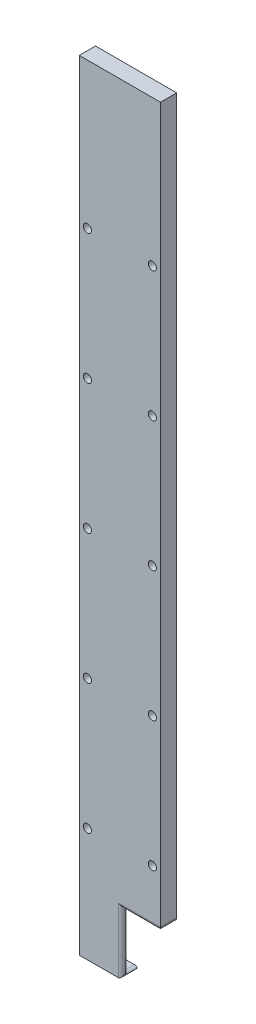
SolidWorks part; units mm, degrees
ref_plane "Front Plane" through (0, 0, 0) normal (0, 0, 1) x (1, 0, 0)
ref_plane "Top Plane" through (0, 0, 0) normal (0, 1, 0) x (1, 0, 0)
ref_plane "Right Plane" through (0, 0, 0) normal (1, 0, 0) x (0, 0, -1)
sketch "Sketch1" plane through (0, 0, 0) normal (0, 0, 1) x (1, 0, 0)
  line L0 (98.3794, 205.2) -> (2.4412, 205.2)
  line L1 (2.4412, 205.2) -> (0.8, 203.5588)
  line L2 (0.8, 203.5588) -> (0.8, 153.025)
  line L3 (0.8, 153.025) -> (2.4412, 151.3838)
  line L8 (86, 134.5838) -> (20, 134.5838) construction
  line L9 (86, 98.5838) -> (86, 134.5838) construction
  line L10 (20, 98.5838) -> (86, 98.5838) construction
  line L11 (20, 134.5838) -> (20, 98.5838) construction
  line L16 (81.145, 81.5838) -> (24.855, 81.5838) construction
  line L17 (84.315, 59.3538) -> (84.315, 78.4138) construction
  line L28 (2.524, 205) -> (1, 203.476) construction
  line L29 (1, 203.476) -> (1, 153.1078) construction
  line L30 (1, 153.1078) -> (2.524, 151.5838) construction
  line L31 (2.524, 151.5838) -> (99.044, 151.5838) construction
  line L32 (99.044, 151.5838) -> (102.6, 155.1398) construction
  line L33 (102.6, 155.1398) -> (102.6, 189.76) construction
  line L34 (102.6, 189.76) -> (100.06, 192.3) construction
  line L35 (100.06, 192.3) -> (100.06, 203.2366) construction
  line L36 (100.06, 203.2366) -> (98.2966, 205) construction
  line L37 (98.2966, 205) -> (2.524, 205) construction
  line L38 (24.855, 56.1838) -> (81.145, 56.1838) construction
  line L39 (21.685, 78.4138) -> (21.685, 59.3538) construction
  line L44 (37.25, 17.6838) -> (68.75, 17.6838) construction
  line L45 (68.75, 17.6838) -> (68.75, 39.1838) construction
  line L46 (68.75, 39.1838) -> (37.25, 39.1838) construction
  line L47 (37.25, 39.1838) -> (37.25, 17.6838) construction
  line L48 (2.4412, 151.3838) -> (99.1268, 151.3838)
  line L49 (99.1268, 151.3838) -> (102.8, 155.057)
  line L50 (102.8, 155.057) -> (102.8, 189.8428) construction
  line L51 (102.8, 189.8428) -> (100.26, 192.3828)
  line L52 (100.26, 192.3828) -> (100.26, 203.3194)
  line L53 (100.26, 203.3194) -> (98.3794, 205.2)
  line L54 (86.2, 134.7838) -> (19.8, 134.7838)
  line L55 (19.8, 134.7838) -> (19.8, 98.3838)
  line L56 (19.8, 98.3838) -> (86.2, 98.3838)
  line L57 (86.2, 98.3838) -> (86.2, 134.7838) construction
  line L58 (81.145, 81.7838) -> (24.855, 81.7838)
  line L59 (21.485, 78.4138) -> (21.485, 59.3538)
  line L60 (24.855, 55.9838) -> (81.145, 55.9838)
  line L61 (84.515, 59.3538) -> (84.515, 78.4138) construction
  line L62 (68.95, 17.4838) -> (68.95, 39.3838) construction
  line L63 (68.95, 39.3838) -> (37.05, 39.3838)
  line L64 (37.05, 39.3838) -> (37.05, 17.4838)
  line L65 (37.05, 17.4838) -> (68.95, 17.4838)
  line L66 (110.8, 177.4499) -> (102.8, 177.4499)
  line L67 (102.8, 177.4499) -> (102.8, 189.8428)
  line L68 (112.8, 175.4499) -> (112.8, 169.4499)
  line L69 (110.8, 167.4499) -> (102.8, 167.4499)
  line L70 (102.8, 155.057) -> (102.8, 167.4499)
  line L71 (86.2, 98.3838) -> (86.2, 111.5838)
  line L72 (86.2, 121.5838) -> (94.2, 121.5838)
  line L73 (96.2, 119.5838) -> (96.2, 113.5838)
  line L74 (94.2, 111.5838) -> (86.2, 111.5838)
  line L75 (86.2, 134.7838) -> (86.2, 121.5838)
  line L77 (84.515, 73.8838) -> (92.515, 73.8838)
  line L78 (94.515, 71.8838) -> (94.515, 65.8838)
  line L79 (92.515, 63.8838) -> (84.515, 63.8838)
  line L80 (84.515, 63.8838) -> (84.515, 59.3538)
  line L81 (68.95, 39.3838) -> (68.95, 34.3838)
  line L82 (68.95, 34.3838) -> (76.95, 34.3838)
  line L83 (78.95, 32.3838) -> (78.95, 24.4838)
  line L84 (76.95, 22.4838) -> (68.95, 22.4838)
  line L85 (68.95, 22.4838) -> (68.95, 17.4838)
  line L89 (102.6, 172.4499) -> (112.8, 172.4499) construction
  line L90 (84.515, 73.8838) -> (84.515, 78.4138)
  line L91 (140, 205.2) -> (150, 205.2) construction
  line L92 (125, 205.2) -> (140, 205.2)
  line L93 (125, 205.2) -> (125, 0)
  line L94 (125, 0) -> (140, 0)
  line L95 (140, 205.2) -> (140, 0)
  line L97 (132.5, 205.2) -> (132.5, 0) construction
  line L99 (142.5, 205.2) -> (142.5, 0) construction
  arc A0 (24.855, 81.7838) -> (21.485, 78.4138) centre (24.855, 78.4138) ccw
  circle A2 centre (22.5, 132.0838) radius 1.6 construction
  circle A4 centre (15.1224, 202.46) radius 1.5621 construction
  circle A6 centre (15.1224, 154.1238) radius 1.5621 construction
  circle A8 centre (97.7486, 154.1238) radius 1.5621 construction
  circle A10 centre (22.5, 101.0838) radius 1.6 construction
  circle A12 centre (83.5, 101.0838) radius 1.6 construction
  circle A14 centre (83.5, 132.0838) radius 1.6 construction
  circle A16 centre (90.2556, 202.46) radius 1.5621 construction
  circle A18 centre (81.135, 59.3638) radius 1.25 construction
  circle A20 centre (81.135, 78.4038) radius 1.25 construction
  circle A22 centre (24.865, 78.4038) radius 1.25 construction
  circle A24 centre (66.25, 28.4338) radius 1.5 construction
  arc A30 (84.315, 78.4138) -> (81.145, 81.5838) centre (81.145, 78.4138) ccw construction
  arc A31 (81.145, 56.1838) -> (84.315, 59.3538) centre (81.145, 59.3538) ccw construction
  arc A32 (21.685, 59.3538) -> (24.855, 56.1838) centre (24.855, 59.3538) ccw construction
  arc A33 (24.855, 81.5838) -> (21.685, 78.4138) centre (24.855, 78.4138) ccw construction
  circle A34 centre (39.75, 28.4338) radius 1.5 construction
  circle A36 centre (24.865, 59.3638) radius 1.25 construction
  arc A37 (21.485, 59.3538) -> (24.855, 55.9838) centre (24.855, 59.3538) ccw
  arc A38 (81.145, 55.9838) -> (84.515, 59.3538) centre (81.145, 59.3538) ccw
  arc A39 (84.515, 78.4138) -> (81.145, 81.7838) centre (81.145, 78.4138) ccw
  arc A40 (78.95, 24.4838) -> (76.95, 22.4838) centre (76.95, 24.4838) cw
  arc A41 (78.95, 32.3838) -> (76.95, 34.3838) centre (76.95, 32.3838) ccw
  arc A42 (94.515, 65.8838) -> (92.515, 63.8838) centre (92.515, 65.8838) cw
  arc A43 (94.515, 71.8838) -> (92.515, 73.8838) centre (92.515, 71.8838) ccw
  arc A44 (96.2, 113.5838) -> (94.2, 111.5838) centre (94.2, 113.5838) cw
  arc A45 (96.2, 119.5838) -> (94.2, 121.5838) centre (94.2, 119.5838) ccw
  arc A46 (112.8, 169.4499) -> (110.8, 167.4499) centre (110.8, 169.4499) cw
  arc A47 (110.8, 177.4499) -> (112.8, 175.4499) centre (110.8, 175.4499) cw
  circle A48 centre (142.5, 182.6) radius 1.25
  circle A49 centre (142.5, 142.6) radius 1.25
  circle A50 centre (142.5, 102.6) radius 1.25
  circle A51 centre (142.5, 62.6) radius 1.25
  circle A52 centre (142.5, 22.6) radius 1.25
  circle A53 centre (122.5, 22.6) radius 1.25
  circle A54 centre (122.5, 102.6) radius 1.25
  circle A55 centre (122.5, 62.6) radius 1.25
  circle A56 centre (122.5, 142.6) radius 1.25
  circle A57 centre (122.5, 182.6) radius 1.25
  point P103 (112.8, 172.4499)
  point P135 (78.95, 34.3838)
  point P138 (94.515, 63.8838)
  point P141 (94.515, 73.8838)
  point P146 (96.2, 121.5838)
  point P149 (112.8, 167.4499)
  point P152 (112.8, 177.4499)
  point P163 (142.5, 102.6)
  dimension "D28" = 2
  dimension "D31" = 2.5
  dimension "D20" = 10
  dimension "D21" = 10
  dimension "D22" = 10
  dimension "D23" = 10
  dimension "D24" = 10
  dimension "D25" = 10
  dimension "D26" = 10
  dimension "D27" = 5
  dimension "D30" = 15
  dimension "D32" = 5
  dimension "D33" = 5
  dimension "D34" = 40
  dimension "D19" = 0.2
sketch "Sketch2" plane through (0, 0, 0) normal (0, 0, 1) x (1, 0, 0)
  line L0 (120, 0) -> (120, -12.5)
  line L1 (120, 227.5) -> (145, 227.5)
  line L2 (120, 227.5) -> (120, 0)
  line L3 (120, 0) -> (145, 0) construction
  line L4 (140, 205.2) -> (125, 205.2)
  line L5 (140, 0) -> (140, 205.2)
  line L6 (125, 0) -> (140, 0)
  line L7 (125, 205.2) -> (125, 0)
  line L8 (76.95, 34.3838) -> (68.95, 34.3838)
  line L9 (68.95, 34.3838) -> (68.95, 39.3838)
  line L10 (68.95, 39.3838) -> (37.05, 39.3838)
  line L11 (37.05, 39.3838) -> (37.05, 17.4838)
  line L12 (37.05, 17.4838) -> (68.95, 17.4838)
  line L13 (68.95, 17.4838) -> (68.95, 22.4838)
  line L14 (68.95, 22.4838) -> (76.95, 22.4838)
  line L15 (78.95, 24.4838) -> (78.95, 32.3838)
  line L16 (76.95, 34.3838) -> (68.95, 34.3838) construction
  line L17 (68.95, 34.3838) -> (68.95, 39.3838) construction
  line L18 (68.95, 39.3838) -> (37.05, 39.3838) construction
  line L19 (37.05, 39.3838) -> (37.05, 17.4838) construction
  line L20 (37.05, 17.4838) -> (68.95, 17.4838) construction
  line L21 (68.95, 17.4838) -> (68.95, 22.4838) construction
  line L22 (68.95, 22.4838) -> (76.95, 22.4838) construction
  line L23 (78.95, 24.4838) -> (78.95, 32.3838) construction
  line L24 (92.515, 73.8838) -> (84.515, 73.8838)
  line L25 (84.515, 73.8838) -> (84.515, 78.4138)
  line L26 (81.145, 81.7838) -> (24.855, 81.7838)
  line L27 (21.485, 78.4138) -> (21.485, 59.3538)
  line L28 (24.855, 55.9838) -> (81.145, 55.9838)
  line L29 (84.515, 59.3538) -> (84.515, 63.8838)
  line L30 (84.515, 63.8838) -> (92.515, 63.8838)
  line L31 (94.515, 65.8838) -> (94.515, 71.8838)
  line L32 (92.515, 73.8838) -> (84.515, 73.8838) construction
  line L33 (84.515, 73.8838) -> (84.515, 78.4138) construction
  line L34 (81.145, 81.7838) -> (24.855, 81.7838) construction
  line L35 (21.485, 78.4138) -> (21.485, 59.3538) construction
  line L36 (24.855, 55.9838) -> (81.145, 55.9838) construction
  line L37 (84.515, 59.3538) -> (84.515, 63.8838) construction
  line L38 (84.515, 63.8838) -> (92.515, 63.8838) construction
  line L39 (94.515, 65.8838) -> (94.515, 71.8838) construction
  line L40 (140, 205.2) -> (125, 205.2) construction
  line L41 (140, 0) -> (140, 205.2) construction
  line L42 (125, 0) -> (140, 0) construction
  line L43 (125, 205.2) -> (125, 0) construction
  line L44 (145, 227.5) -> (145, 0)
  line L45 (120, -12.5) -> (145, -12.5)
  line L46 (145, -12.5) -> (145, 0)
  line L48 (94.2, 121.5838) -> (86.2, 121.5838)
  line L49 (86.2, 121.5838) -> (86.2, 134.7838)
  line L50 (86.2, 134.7838) -> (19.8, 134.7838)
  line L51 (19.8, 134.7838) -> (19.8, 98.3838)
  line L52 (19.8, 98.3838) -> (86.2, 98.3838)
  line L53 (86.2, 98.3838) -> (86.2, 111.5838)
  line L54 (86.2, 111.5838) -> (94.2, 111.5838)
  line L55 (96.2, 113.5838) -> (96.2, 119.5838)
  line L56 (94.2, 121.5838) -> (86.2, 121.5838) construction
  line L57 (86.2, 121.5838) -> (86.2, 134.7838) construction
  line L58 (86.2, 134.7838) -> (19.8, 134.7838) construction
  line L59 (19.8, 134.7838) -> (19.8, 98.3838) construction
  line L60 (19.8, 98.3838) -> (86.2, 98.3838) construction
  line L61 (86.2, 98.3838) -> (86.2, 111.5838) construction
  line L62 (86.2, 111.5838) -> (94.2, 111.5838) construction
  line L63 (96.2, 113.5838) -> (96.2, 119.5838) construction
  line L70 (110.8, 177.4499) -> (102.8, 177.4499)
  line L71 (102.8, 177.4499) -> (102.8, 189.8428)
  line L72 (102.8, 189.8428) -> (100.26, 192.3828)
  line L73 (100.26, 192.3828) -> (100.26, 203.3194)
  line L74 (100.26, 203.3194) -> (98.3794, 205.2)
  line L75 (98.3794, 205.2) -> (2.4412, 205.2)
  line L76 (2.4412, 205.2) -> (0.8, 203.5588)
  line L77 (0.8, 203.5588) -> (0.8, 153.025)
  line L78 (0.8, 153.025) -> (2.4412, 151.3838)
  line L79 (2.4412, 151.3838) -> (99.1268, 151.3838)
  line L80 (99.1268, 151.3838) -> (102.8, 155.057)
  line L81 (102.8, 155.057) -> (102.8, 167.4499)
  line L82 (102.8, 167.4499) -> (110.8, 167.4499)
  line L83 (112.8, 169.4499) -> (112.8, 175.4499)
  line L84 (110.8, 177.4499) -> (102.8, 177.4499) construction
  line L85 (102.8, 177.4499) -> (102.8, 189.8428) construction
  line L86 (102.8, 189.8428) -> (100.26, 192.3828) construction
  line L87 (100.26, 192.3828) -> (100.26, 203.3194) construction
  line L88 (100.26, 203.3194) -> (98.3794, 205.2) construction
  line L89 (98.3794, 205.2) -> (2.4412, 205.2) construction
  line L90 (2.4412, 205.2) -> (0.8, 203.5588) construction
  line L91 (0.8, 203.5588) -> (0.8, 153.025) construction
  line L92 (0.8, 153.025) -> (2.4412, 151.3838) construction
  line L93 (2.4412, 151.3838) -> (99.1268, 151.3838) construction
  line L94 (99.1268, 151.3838) -> (102.8, 155.057) construction
  line L95 (102.8, 155.057) -> (102.8, 167.4499) construction
  line L96 (102.8, 167.4499) -> (110.8, 167.4499) construction
  line L97 (112.8, 169.4499) -> (112.8, 175.4499) construction
  circle A1 centre (142.5, 22.6) radius 1.25
  arc A2 (76.95, 22.4838) -> (78.95, 24.4838) centre (76.95, 24.4838) ccw
  arc A3 (78.95, 32.3838) -> (76.95, 34.3838) centre (76.95, 32.3838) ccw
  arc A4 (76.95, 22.4838) -> (78.95, 24.4838) centre (76.95, 24.4838) ccw construction
  arc A5 (78.95, 32.3838) -> (76.95, 34.3838) centre (76.95, 32.3838) ccw construction
  arc A6 (94.2, 111.5838) -> (96.2, 113.5838) centre (94.2, 113.5838) ccw
  arc A7 (96.2, 119.5838) -> (94.2, 121.5838) centre (94.2, 119.5838) ccw
  arc A8 (94.2, 111.5838) -> (96.2, 113.5838) centre (94.2, 113.5838) ccw construction
  arc A9 (96.2, 119.5838) -> (94.2, 121.5838) centre (94.2, 119.5838) ccw construction
  arc A10 (84.515, 78.4138) -> (81.145, 81.7838) centre (81.145, 78.4138) ccw
  arc A11 (24.855, 81.7838) -> (21.485, 78.4138) centre (24.855, 78.4138) ccw
  arc A12 (21.485, 59.3538) -> (24.855, 55.9838) centre (24.855, 59.3538) ccw
  arc A13 (81.145, 55.9838) -> (84.515, 59.3538) centre (81.145, 59.3538) ccw
  arc A14 (92.515, 63.8838) -> (94.515, 65.8838) centre (92.515, 65.8838) ccw
  arc A15 (94.515, 71.8838) -> (92.515, 73.8838) centre (92.515, 71.8838) ccw
  arc A16 (84.515, 78.4138) -> (81.145, 81.7838) centre (81.145, 78.4138) ccw construction
  arc A17 (24.855, 81.7838) -> (21.485, 78.4138) centre (24.855, 78.4138) ccw construction
  arc A18 (21.485, 59.3538) -> (24.855, 55.9838) centre (24.855, 59.3538) ccw construction
  arc A19 (81.145, 55.9838) -> (84.515, 59.3538) centre (81.145, 59.3538) ccw construction
  arc A20 (92.515, 63.8838) -> (94.515, 65.8838) centre (92.515, 65.8838) ccw construction
  arc A21 (94.515, 71.8838) -> (92.515, 73.8838) centre (92.515, 71.8838) ccw construction
  arc A22 (110.8, 167.4499) -> (112.8, 169.4499) centre (110.8, 169.4499) ccw
  arc A23 (112.8, 175.4499) -> (110.8, 177.4499) centre (110.8, 175.4499) ccw
  arc A24 (110.8, 167.4499) -> (112.8, 169.4499) centre (110.8, 169.4499) ccw construction
  arc A25 (112.8, 175.4499) -> (110.8, 177.4499) centre (110.8, 175.4499) ccw construction
  circle A26 centre (142.5, 22.6) radius 1.25
  circle A27 centre (142.5, 62.6) radius 1.25
  circle A28 centre (142.5, 62.6) radius 1.25
  circle A29 centre (142.5, 102.6) radius 1.25
  circle A30 centre (142.5, 102.6) radius 1.25
  circle A31 centre (142.5, 142.6) radius 1.25
  circle A32 centre (142.5, 142.6) radius 1.25
  circle A33 centre (142.5, 182.6) radius 1.25
  circle A34 centre (142.5, 182.6) radius 1.25
  circle A35 centre (122.5, 182.6) radius 1.25
  circle A36 centre (122.5, 182.6) radius 1.25
  circle A37 centre (122.5, 142.6) radius 1.25
  circle A38 centre (122.5, 142.6) radius 1.25
  circle A39 centre (122.5, 62.6) radius 1.25
  circle A40 centre (122.5, 62.6) radius 1.25
  circle A41 centre (122.5, 102.6) radius 1.25
  circle A42 centre (122.5, 102.6) radius 1.25
  circle A43 centre (122.5, 22.6) radius 1.25
  circle A44 centre (122.5, 22.6) radius 1.25
  dimension "D16" = 25
  dimension "D17" = 227.5
  dimension "D18" = 5
  dimension "D19" = 12.5
  dimension "D1" = 0
  dimension "D2" = 0
  dimension "D3" = 0
  dimension "D4" = 0
  dimension "D5" = 0
  dimension "D6" = 0
  dimension "D7" = 0
  dimension "D8" = 0
  dimension "D9" = 0
  dimension "D10" = 0
  dimension "D11" = 0
  dimension "D12" = 0
  dimension "D13" = 0
  dimension "D14" = 0
  dimension "D15" = 0
extrude "Boss-Extrude1" add sketch "Sketch2" along normal blind 5
sketch "Sketch3" plane through (0, 0, 0) normal (0, 0, -1) x (-1, 0, 0)
  line L0 (-125, 177.6) -> (-120, 177.6)
  line L1 (-120, 227.5) -> (-120, -12.5) construction
  line L2 (-125, 162.6) -> (-120, 162.6)
  line L3 (-125, 127.6) -> (-120, 127.6)
  line L4 (-125, 205.2) -> (-140, 205.2)
  line L5 (-140, 205.2) -> (-140, 0)
  line L6 (-140, 0) -> (-125, 0)
  line L7 (-125, 0) -> (-125, 205.2)
  line L8 (-68.95, 34.3838) -> (-76.95, 34.3838)
  line L9 (-68.95, 39.3838) -> (-68.95, 34.3838)
  line L10 (-37.05, 39.3838) -> (-68.95, 39.3838)
  line L11 (-37.05, 17.4838) -> (-37.05, 39.3838)
  line L12 (-68.95, 17.4838) -> (-37.05, 17.4838)
  line L13 (-68.95, 22.4838) -> (-68.95, 17.4838)
  line L14 (-76.95, 22.4838) -> (-68.95, 22.4838)
  line L15 (-78.95, 32.3838) -> (-78.95, 24.4838)
  line L16 (-68.95, 34.3838) -> (-76.95, 34.3838) construction
  line L17 (-68.95, 39.3838) -> (-68.95, 34.3838) construction
  line L18 (-37.05, 39.3838) -> (-68.95, 39.3838) construction
  line L19 (-37.05, 17.4838) -> (-37.05, 39.3838) construction
  line L20 (-68.95, 17.4838) -> (-37.05, 17.4838) construction
  line L21 (-68.95, 22.4838) -> (-68.95, 17.4838) construction
  line L22 (-76.95, 22.4838) -> (-68.95, 22.4838) construction
  line L23 (-78.95, 32.3838) -> (-78.95, 24.4838) construction
  line L24 (-84.515, 73.8838) -> (-92.515, 73.8838)
  line L25 (-84.515, 78.4138) -> (-84.515, 73.8838)
  line L26 (-24.855, 81.7838) -> (-81.145, 81.7838)
  line L27 (-21.485, 59.3538) -> (-21.485, 78.4138)
  line L28 (-81.145, 55.9838) -> (-24.855, 55.9838)
  line L29 (-84.515, 63.8838) -> (-84.515, 59.3538)
  line L30 (-92.515, 63.8838) -> (-84.515, 63.8838)
  line L31 (-94.515, 71.8838) -> (-94.515, 65.8838)
  line L32 (-84.515, 73.8838) -> (-92.515, 73.8838) construction
  line L33 (-84.515, 78.4138) -> (-84.515, 73.8838) construction
  line L34 (-24.855, 81.7838) -> (-81.145, 81.7838) construction
  line L35 (-21.485, 59.3538) -> (-21.485, 78.4138) construction
  line L36 (-81.145, 55.9838) -> (-24.855, 55.9838) construction
  line L37 (-84.515, 63.8838) -> (-84.515, 59.3538) construction
  line L38 (-92.515, 63.8838) -> (-84.515, 63.8838) construction
  line L39 (-94.515, 71.8838) -> (-94.515, 65.8838) construction
  line L40 (-125, 205.2) -> (-140, 205.2)
  line L41 (-140, 205.2) -> (-140, 0) construction
  line L43 (-125, 0) -> (-125, 205.2) construction
  line L44 (-125, 112.6) -> (-120, 112.6)
  line L45 (-125, 82.6) -> (-120, 82.6)
  line L46 (-125, 67.6) -> (-120, 67.6)
  line L47 (-125, 42.6) -> (-120, 42.6)
  line L48 (-86.2, 121.5838) -> (-94.2, 121.5838)
  line L49 (-86.2, 134.7838) -> (-86.2, 121.5838)
  line L50 (-19.8, 134.7838) -> (-86.2, 134.7838)
  line L51 (-19.8, 98.3838) -> (-19.8, 134.7838)
  line L52 (-86.2, 98.3838) -> (-19.8, 98.3838)
  line L53 (-86.2, 111.5838) -> (-86.2, 98.3838)
  line L54 (-94.2, 111.5838) -> (-86.2, 111.5838)
  line L55 (-96.2, 119.5838) -> (-96.2, 113.5838)
  line L56 (-86.2, 121.5838) -> (-94.2, 121.5838) construction
  line L57 (-86.2, 134.7838) -> (-86.2, 121.5838) construction
  line L58 (-19.8, 134.7838) -> (-86.2, 134.7838) construction
  line L59 (-19.8, 98.3838) -> (-19.8, 134.7838) construction
  line L60 (-86.2, 98.3838) -> (-19.8, 98.3838) construction
  line L61 (-86.2, 111.5838) -> (-86.2, 98.3838) construction
  line L62 (-94.2, 111.5838) -> (-86.2, 111.5838) construction
  line L63 (-96.2, 119.5838) -> (-96.2, 113.5838) construction
  line L64 (-125, 27.6) -> (-120, 27.6)
  line L65 (-125, 205.2) -> (-125, 177.6)
  line L66 (-120, 177.6) -> (-120, 162.6)
  line L67 (-125, 162.6) -> (-125, 127.6)
  line L68 (-120, 127.6) -> (-120, 112.6)
  line L69 (-125, 112.6) -> (-125, 82.6)
  line L70 (-102.8, 177.4499) -> (-110.8, 177.4499)
  line L71 (-102.8, 189.8428) -> (-102.8, 177.4499)
  line L72 (-100.26, 192.3828) -> (-102.8, 189.8428)
  line L73 (-100.26, 203.3194) -> (-100.26, 192.3828)
  line L74 (-98.3794, 205.2) -> (-100.26, 203.3194)
  line L75 (-2.4412, 205.2) -> (-98.3794, 205.2)
  line L76 (-0.8, 203.5588) -> (-2.4412, 205.2)
  line L77 (-0.8, 153.025) -> (-0.8, 203.5588)
  line L78 (-2.4412, 151.3838) -> (-0.8, 153.025)
  line L79 (-99.1268, 151.3838) -> (-2.4412, 151.3838)
  line L80 (-102.8, 155.057) -> (-99.1268, 151.3838)
  line L81 (-102.8, 167.4499) -> (-102.8, 155.057)
  line L82 (-110.8, 167.4499) -> (-102.8, 167.4499)
  line L83 (-112.8, 175.4499) -> (-112.8, 169.4499)
  line L84 (-102.8, 177.4499) -> (-110.8, 177.4499) construction
  line L85 (-102.8, 189.8428) -> (-102.8, 177.4499) construction
  line L86 (-100.26, 192.3828) -> (-102.8, 189.8428) construction
  line L87 (-100.26, 203.3194) -> (-100.26, 192.3828) construction
  line L88 (-98.3794, 205.2) -> (-100.26, 203.3194) construction
  line L89 (-2.4412, 205.2) -> (-98.3794, 205.2) construction
  line L90 (-0.8, 203.5588) -> (-2.4412, 205.2) construction
  line L91 (-0.8, 153.025) -> (-0.8, 203.5588) construction
  line L92 (-2.4412, 151.3838) -> (-0.8, 153.025) construction
  line L93 (-99.1268, 151.3838) -> (-2.4412, 151.3838) construction
  line L94 (-102.8, 155.057) -> (-99.1268, 151.3838) construction
  line L95 (-102.8, 167.4499) -> (-102.8, 155.057) construction
  line L96 (-110.8, 167.4499) -> (-102.8, 167.4499) construction
  line L97 (-112.8, 175.4499) -> (-112.8, 169.4499) construction
  line L98 (-120, 82.6) -> (-120, 67.6)
  line L99 (-125, 67.6) -> (-125, 42.6)
  line L100 (-120, 42.6) -> (-120, 27.6)
  line L104 (-145, -12.5) -> (-145, 227.5) construction
  line L105 (-145, -11.5) -> (-145, 6.5)
  line L106 (-145, 6.5) -> (-140, 6.5)
  line L107 (-140, 6.5) -> (-140, 205.2)
  line L110 (-120, -12.5) -> (-145, -12.5) construction
  line L113 (-145, -11.5) -> (-125, -11.5)
  line L114 (-125, -11.5) -> (-125, 0)
  line L115 (-125, 27.6) -> (-125, 0)
  circle A1 centre (-142.5, 22.6) radius 1.25
  arc A2 (-78.95, 24.4838) -> (-76.95, 22.4838) centre (-76.95, 24.4838) ccw
  arc A3 (-76.95, 34.3838) -> (-78.95, 32.3838) centre (-76.95, 32.3838) ccw
  arc A4 (-78.95, 24.4838) -> (-76.95, 22.4838) centre (-76.95, 24.4838) ccw construction
  arc A5 (-76.95, 34.3838) -> (-78.95, 32.3838) centre (-76.95, 32.3838) ccw construction
  arc A6 (-96.2, 113.5838) -> (-94.2, 111.5838) centre (-94.2, 113.5838) ccw
  arc A7 (-94.2, 121.5838) -> (-96.2, 119.5838) centre (-94.2, 119.5838) ccw
  arc A8 (-96.2, 113.5838) -> (-94.2, 111.5838) centre (-94.2, 113.5838) ccw construction
  arc A9 (-94.2, 121.5838) -> (-96.2, 119.5838) centre (-94.2, 119.5838) ccw construction
  arc A10 (-81.145, 81.7838) -> (-84.515, 78.4138) centre (-81.145, 78.4138) ccw
  arc A11 (-21.485, 78.4138) -> (-24.855, 81.7838) centre (-24.855, 78.4138) ccw
  arc A12 (-24.855, 55.9838) -> (-21.485, 59.3538) centre (-24.855, 59.3538) ccw
  arc A13 (-84.515, 59.3538) -> (-81.145, 55.9838) centre (-81.145, 59.3538) ccw
  arc A14 (-94.515, 65.8838) -> (-92.515, 63.8838) centre (-92.515, 65.8838) ccw
  arc A15 (-92.515, 73.8838) -> (-94.515, 71.8838) centre (-92.515, 71.8838) ccw
  arc A16 (-81.145, 81.7838) -> (-84.515, 78.4138) centre (-81.145, 78.4138) ccw construction
  arc A17 (-21.485, 78.4138) -> (-24.855, 81.7838) centre (-24.855, 78.4138) ccw construction
  arc A18 (-24.855, 55.9838) -> (-21.485, 59.3538) centre (-24.855, 59.3538) ccw construction
  arc A19 (-84.515, 59.3538) -> (-81.145, 55.9838) centre (-81.145, 59.3538) ccw construction
  arc A20 (-94.515, 65.8838) -> (-92.515, 63.8838) centre (-92.515, 65.8838) ccw construction
  arc A21 (-92.515, 73.8838) -> (-94.515, 71.8838) centre (-92.515, 71.8838) ccw construction
  arc A22 (-112.8, 169.4499) -> (-110.8, 167.4499) centre (-110.8, 169.4499) ccw
  arc A23 (-110.8, 177.4499) -> (-112.8, 175.4499) centre (-110.8, 175.4499) ccw
  arc A24 (-112.8, 169.4499) -> (-110.8, 167.4499) centre (-110.8, 169.4499) ccw construction
  arc A25 (-110.8, 177.4499) -> (-112.8, 175.4499) centre (-110.8, 175.4499) ccw construction
  circle A26 centre (-142.5, 22.6) radius 1.25 construction
  circle A27 centre (-142.5, 62.6) radius 1.25
  circle A28 centre (-142.5, 62.6) radius 1.25 construction
  circle A29 centre (-142.5, 102.6) radius 1.25
  circle A30 centre (-142.5, 102.6) radius 1.25 construction
  circle A31 centre (-142.5, 142.6) radius 1.25
  circle A32 centre (-142.5, 142.6) radius 1.25 construction
  circle A33 centre (-142.5, 182.6) radius 1.25
  circle A34 centre (-142.5, 182.6) radius 1.25 construction
  circle A35 centre (-122.5, 182.6) radius 1.25
  circle A36 centre (-122.5, 182.6) radius 1.25 construction
  circle A37 centre (-122.5, 142.6) radius 1.25
  circle A38 centre (-122.5, 142.6) radius 1.25 construction
  circle A39 centre (-122.5, 62.6) radius 1.25
  circle A40 centre (-122.5, 62.6) radius 1.25 construction
  circle A41 centre (-122.5, 102.6) radius 1.25
  circle A42 centre (-122.5, 102.6) radius 1.25 construction
  circle A43 centre (-122.5, 22.6) radius 1.25
  circle A44 centre (-122.5, 22.6) radius 1.25 construction
  dimension "D19" = 5
  dimension "D23" = 5
  dimension "D16" = 15
  dimension "D17" = 5
  dimension "D18" = 15
  dimension "D20" = 15
  dimension "D21" = 10
  dimension "D22" = 15
  dimension "D24" = 1
  dimension "D25" = 18
  dimension "D1" = 0
  dimension "D2" = 0
  dimension "D3" = 0
  dimension "D4" = 0
  dimension "D5" = 0
  dimension "D6" = 0
  dimension "D7" = 0
  dimension "D8" = 0
  dimension "D9" = 0
  dimension "D10" = 0
  dimension "D11" = 0
  dimension "D12" = 0
  dimension "D13" = 0
  dimension "D14" = 0
  dimension "D15" = 0
extrude "Cut-Extrude1" cut sketch "Sketch3" against normal blind 3
sketch "Sketch4" plane through (0, 0, 0) normal (0, 0, -1) x (-1, 0, 0)
  line L0 (-140, 6.5) -> (-145, 6.5) construction
  line L1 (-145, -12.5) -> (-133, -12.5)
  line L2 (-145, -12.5) -> (-145, 6.5)
  line L3 (-145, 6.5) -> (-133, 6.5)
  line L4 (-133, -12.5) -> (-133, 6.5)
  dimension "D1" = 12
extrude "Cut-Extrude2" cut sketch "Sketch4" against normal blind 10
fillet "Fillet1" radius 1 20 edges at (133, -2.5, 3) (133, -3, 5) (133, -12.5, 2.5) (133, -11.5, 1.5) (145, 6.5, 2.5) (140, 6.5, 1.5) (136.5, 6.5, 3) (139, 6.5, 5) (120, 42.6, 1.5) (120, 35.1, 3) (120, 27.6, 1.5) (120, 67.6, 1.5) (120, 75.1, 3) (120, 82.6, 1.5) (120, 127.6, 1.5) (120, 120.1, 3) (120, 112.6, 1.5) (120, 177.6, 1.5) (120, 170.1, 3) (120, 162.6, 1.5)
